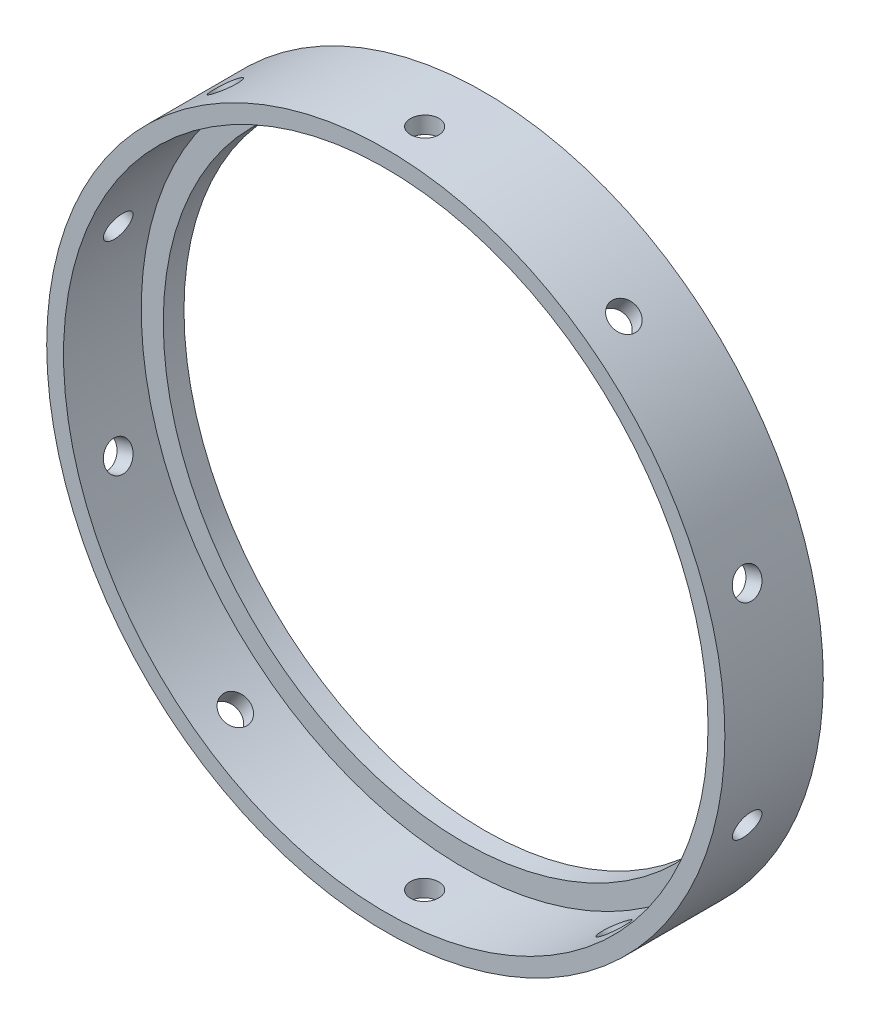
SolidWorks part; units mm, degrees
ref_plane "Front Plane" through (0, 0, 0) normal (0, 0, 1) x (1, 0, 0)
ref_plane "Top Plane" through (0, 0, 0) normal (0, 1, 0) x (1, 0, 0)
ref_plane "Right Plane" through (0, 0, 0) normal (1, 0, 0) x (0, 0, -1)
sketch "Sketch1" plane through (0, 0, 0) normal (0, 0, 1) x (1, 0, 0)
  circle A0 centre (0, 0) radius 78.994
  circle A1 centre (0, 0) radius 83.1215
  dimension "D1" = 157.988
  dimension "D2" = 166.243
extrude "Boss-Extrude1" add sketch "Sketch1" along normal blind 19.05
sketch "Sketch2" plane through (0, 0, 0) normal (0, 1, 0) x (1, 0, 0)
  line L0 (78.994, 0) -> (-78.994, 0) construction
  line L1 (0, -2.0807) -> (0, -15.8358) construction
  circle A0 centre (0, -9.525) radius 3.4782
  dimension "D1" = 9.525
extrude "Cut-Extrude1" cut sketch "Sketch2" against normal through all
ref_axis "Axis1" through (0, 0, 2.0807) along (0, 0, 1)
pattern_circular "CirPattern1" count 10 over 360 about axis through (0, 0, 2.0807) along (0, 0, 1) of "Cut-Extrude1"
sketch "Sketch3" plane through (0, 0, 0) normal (0, 0, -1) x (-1, 0, 0)
  circle A0 centre (0, 0) radius 83.1215
  circle A1 centre (0, 0) radius 73.5965
  dimension "D1" = 166.243
  dimension "D2" = 147.193
extrude "Boss-Extrude2" add sketch "Sketch3" along normal blind 5.08
